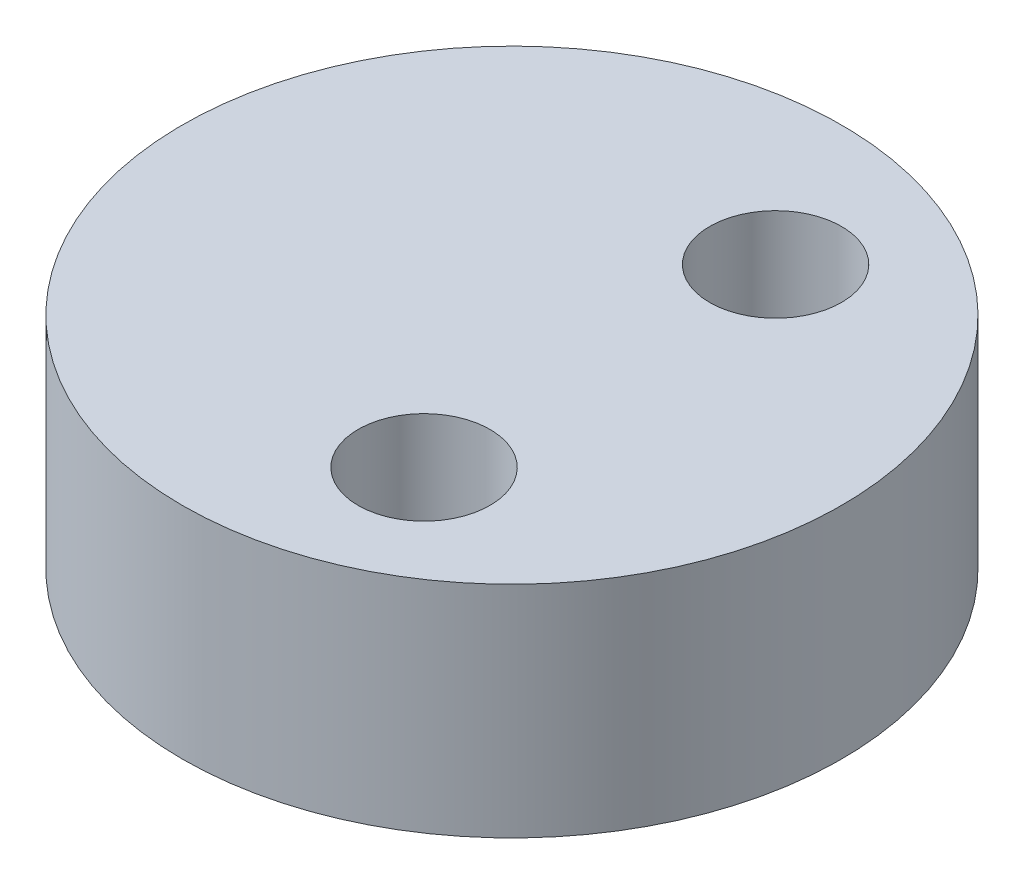
SolidWorks part; units mm, degrees
ref_plane "Front Plane" through (0, 0, 0) normal (0, 0, 1) x (1, 0, 0)
ref_plane "Top Plane" through (0, 0, 0) normal (0, 1, 0) x (1, 0, 0)
ref_plane "Right Plane" through (0, 0, 0) normal (1, 0, 0) x (0, 0, -1)
sketch "Sketch1" plane through (0, 0, 0) normal (0, 1, 0) x (1, 0, 0)
  line L0 (0, 0) -> (-2, 0) construction
  circle A0 centre (0, 0) radius 4 construction
  circle A1 centre (-2, 0) radius 7.5
  circle A3 centre (0, 4) radius 1.5
  circle A4 centre (0, -4) radius 1.5
  point P12 (0, 0)
  dimension "D1" = 8
  dimension "D3" = 15
  dimension "D5" = 3
  dimension "D2" = 2
  dimension "D6" = 2
extrude "Boss-Extrude1" add sketch "Sketch1" along normal blind 5
